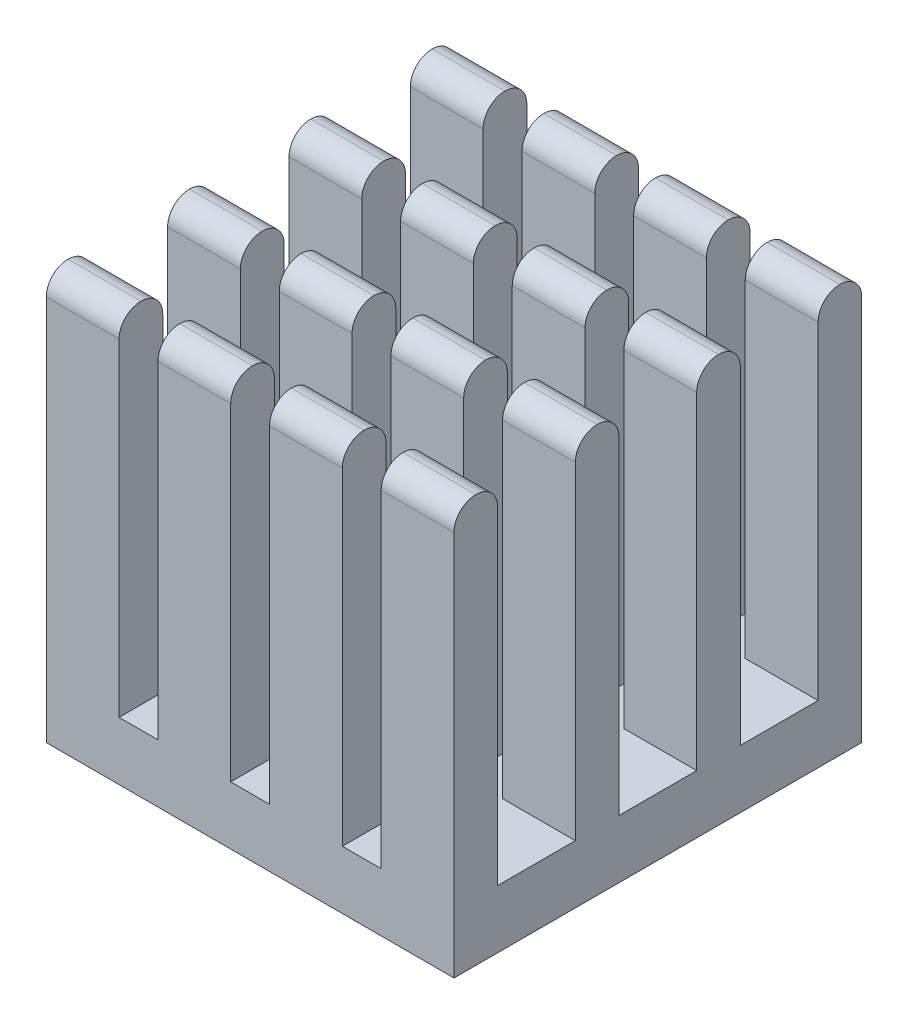
SolidWorks part; units mm, degrees
ref_plane "Front Plane" through (0, 0, 0) normal (0, 0, 1) x (1, 0, 0)
ref_plane "Top Plane" through (0, 0, 0) normal (0, 1, 0) x (1, 0, 0)
ref_plane "Right Plane" through (0, 0, 0) normal (1, 0, 0) x (0, 0, -1)
sketch "Sketch1" plane through (0, 0, 0) normal (0, 1, 0) x (1, 0, 0)
  line L1 (0, 0) -> (14, 0)
  line L2 (0, 0) -> (0, 14)
  line L3 (0, 14) -> (14, 14)
  line L4 (14, 0) -> (14, 14)
  dimension "D1" = 14
  dimension "D2" = 14
extrude "Boss-Extrude1" add sketch "Sketch1" along normal blind 2
sketch "Sketch2" plane through (0, 2, 0) normal (0, 1, 0) x (1, 0, 0)
  line L0 (3.8333, 0) -> (3.8333, 1.5)
  line L1 (0, 0) -> (2.5, 0)
  line L2 (0, 0) -> (0, 1.5)
  line L3 (0, 1.5) -> (2.5, 1.5)
  line L4 (2.5, 0) -> (2.5, 1.5)
  line L5 (3.8333, 0) -> (6.3333, 0)
  line L6 (6.3333, 0) -> (6.3333, 1.5)
  line L7 (3.8333, 1.5) -> (6.3333, 1.5)
  line L8 (7.6667, 0) -> (7.6667, 1.5)
  line L9 (7.6667, 0) -> (10.1667, 0)
  line L10 (10.1667, 0) -> (10.1667, 1.5)
  line L11 (7.6667, 1.5) -> (10.1667, 1.5)
  line L12 (11.5, 0) -> (11.5, 1.5)
  line L13 (11.5, 0) -> (14, 0)
  line L14 (14, 0) -> (14, 1.5)
  line L15 (11.5, 1.5) -> (14, 1.5)
  line L16 (3.8333, 4.1667) -> (3.8333, 5.6667)
  line L17 (3.8333, 4.1667) -> (6.3333, 4.1667)
  line L18 (6.3333, 4.1667) -> (6.3333, 5.6667)
  line L19 (3.8333, 5.6667) -> (6.3333, 5.6667)
  line L20 (7.6667, 4.1667) -> (7.6667, 5.6667)
  line L21 (7.6667, 4.1667) -> (10.1667, 4.1667)
  line L22 (10.1667, 4.1667) -> (10.1667, 5.6667)
  line L23 (7.6667, 5.6667) -> (10.1667, 5.6667)
  line L24 (11.5, 4.1667) -> (11.5, 5.6667)
  line L25 (11.5, 4.1667) -> (14, 4.1667)
  line L26 (14, 4.1667) -> (14, 5.6667)
  line L27 (11.5, 5.6667) -> (14, 5.6667)
  line L28 (3.8333, 8.3333) -> (3.8333, 9.8333)
  line L29 (3.8333, 8.3333) -> (6.3333, 8.3333)
  line L30 (6.3333, 8.3333) -> (6.3333, 9.8333)
  line L31 (3.8333, 9.8333) -> (6.3333, 9.8333)
  line L32 (7.6667, 8.3333) -> (7.6667, 9.8333)
  line L33 (7.6667, 8.3333) -> (10.1667, 8.3333)
  line L34 (10.1667, 8.3333) -> (10.1667, 9.8333)
  line L35 (7.6667, 9.8333) -> (10.1667, 9.8333)
  line L36 (11.5, 8.3333) -> (11.5, 9.8333)
  line L37 (11.5, 8.3333) -> (14, 8.3333)
  line L38 (14, 8.3333) -> (14, 9.8333)
  line L39 (11.5, 9.8333) -> (14, 9.8333)
  line L40 (3.8333, 12.5) -> (3.8333, 14)
  line L41 (3.8333, 12.5) -> (6.3333, 12.5)
  line L42 (6.3333, 12.5) -> (6.3333, 14)
  line L43 (3.8333, 14) -> (6.3333, 14)
  line L44 (7.6667, 12.5) -> (7.6667, 14)
  line L45 (7.6667, 12.5) -> (10.1667, 12.5)
  line L46 (10.1667, 12.5) -> (10.1667, 14)
  line L47 (7.6667, 14) -> (10.1667, 14)
  line L48 (11.5, 12.5) -> (11.5, 14)
  line L49 (11.5, 12.5) -> (14, 12.5)
  line L50 (14, 12.5) -> (14, 14)
  line L51 (11.5, 14) -> (14, 14)
  line L52 (0, 4.1667) -> (0, 5.6667)
  line L53 (0, 4.1667) -> (2.5, 4.1667)
  line L54 (2.5, 4.1667) -> (2.5, 5.6667)
  line L55 (0, 5.6667) -> (2.5, 5.6667)
  line L56 (0, 8.3333) -> (0, 9.8333)
  line L57 (0, 8.3333) -> (2.5, 8.3333)
  line L58 (2.5, 8.3333) -> (2.5, 9.8333)
  line L59 (0, 9.8333) -> (2.5, 9.8333)
  line L60 (0, 12.5) -> (0, 14)
  line L61 (0, 12.5) -> (2.5, 12.5)
  line L62 (2.5, 12.5) -> (2.5, 14)
  line L63 (0, 14) -> (2.5, 14)
  line L65 (0, 14) -> (0, 0) construction
  dimension "D1" = 2.5
  dimension "D2" = 1.5
  dimension "D5" = 2.6667
  dimension "D6" = 0
  dimension "D7" = 1.3333
  dimension "D3" = 4
  dimension "D4" = 4
extrude "Boss-Extrude2" add sketch "Sketch2" along normal blind 12
fillet "Fillet1" radius 0.75 32 edges at (12.75, 14, -12.5) (8.9167, 14, -12.5) (5.0833, 14, -12.5) (1.25, 14, -12.5) (1.25, 14, -14) (5.0833, 14, -14) (8.9167, 14, -14) (12.75, 14, -14) (12.75, 14, -9.8333) (8.9167, 14, -9.8333) (5.0833, 14, -9.8333) (1.25, 14, -9.8333) (1.25, 14, -8.3333) (5.0833, 14, -8.3333) (8.9167, 14, -8.3333) (12.75, 14, -8.3333) (8.9167, 14, -5.6667) (12.75, 14, -5.6667) (5.0833, 14, -5.6667) (1.25, 14, -5.6667) (1.25, 14, -4.1667) (5.0833, 14, -4.1667) (8.9167, 14, -4.1667) (12.75, 14, -4.1667) (8.9167, 14, 0) (12.75, 14, 0) (12.75, 14, -1.5) (8.9167, 14, -1.5) (5.0833, 14, -1.5) (5.0833, 14, 0) (1.25, 14, -1.5) (1.25, 14, 0)
